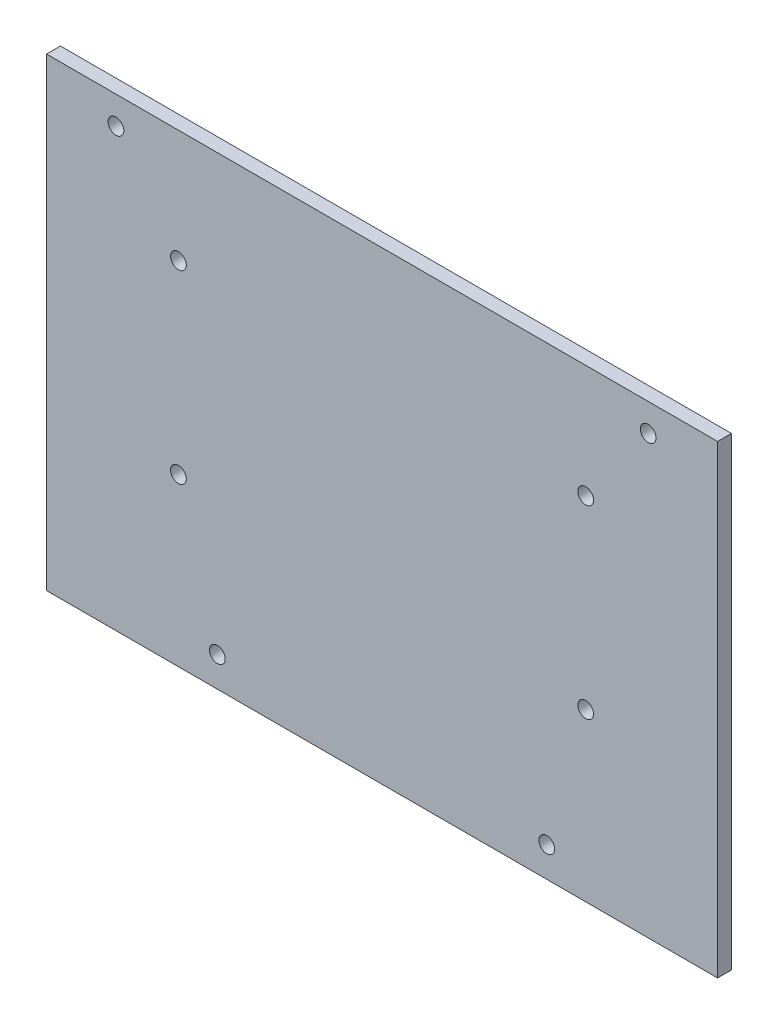
SolidWorks part; units mm, degrees
ref_plane "Front Plane" through (0, 0, 0) normal (0, 0, 1) x (1, 0, 0)
ref_plane "Top Plane" through (0, 0, 0) normal (0, 1, 0) x (1, 0, 0)
ref_plane "Right Plane" through (0, 0, 0) normal (1, 0, 0) x (0, 0, -1)
sketch "Sketch1" plane through (0, 0, 0) normal (0, 0, 1) x (1, 0, 0)
  line L0 (-72.5, 100.4) -> (-76.5, 100.4) construction
  line L1 (-72.5, 0) -> (72.5, 0)
  line L2 (-72.5, 0) -> (-72.5, 100.4)
  line L3 (-72.5, 100.4) -> (72.5, 100.4)
  line L4 (72.5, 0) -> (72.5, 100.4)
  line L5 (0, 0) -> (0, 100.4) construction
  circle A0 centre (-56.5, 6.5) radius 1.7 construction
  circle A1 centre (56.5, 6.5) radius 1.7 construction
  dimension "D2" = 3.4
  dimension "D3" = 16
  dimension "D4" = 6.5
  dimension "D5" = 145
extrude "Boss-Extrude1" add sketch "Sketch1" along normal blind 3
sketch "Sketch3" plane through (0, 0, 3) normal (0, 0, 1) x (1, 0, 0)
  circle A0 centre (-57.5, 94.4) radius 1.7
  circle A1 centre (57.5, 94.4) radius 1.7
  circle A2 centre (-44, 75.9829) radius 1.7
  circle A3 centre (-44, 35.9829) radius 1.7
  circle A4 centre (44, 35.9829) radius 1.7
  circle A5 centre (44, 75.9829) radius 1.7
  circle A6 centre (-35.5875, 6.5) radius 1.7
  circle A7 centre (35.5875, 6.5) radius 1.7
  dimension "D1" = 3.4
  dimension "D2" = 3.4
  dimension "D3" = 3.4
extrude "dependent_holes" cut sketch "Sketch3" against normal blind 10
